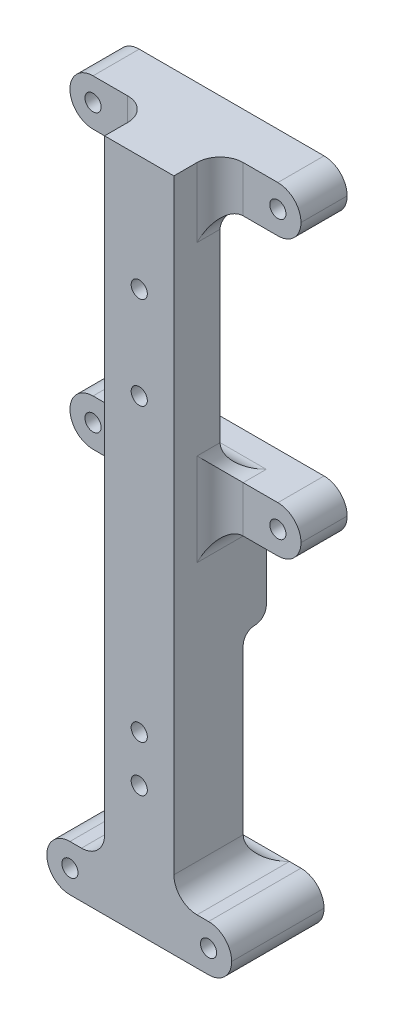
SolidWorks part; units mm, degrees
ref_plane "Front Plane" through (0, 0, 0) normal (0, 0, 1) x (1, 0, 0)
ref_plane "Top Plane" through (0, 0, 0) normal (0, 1, 0) x (1, 0, 0)
ref_plane "Right Plane" through (0, 0, 0) normal (1, 0, 0) x (0, 0, -1)
sketch "Sketch1" plane through (0, 0, 0) normal (0, 0, 1) x (1, 0, 0)
  line L1 (-25, 35) -> (25, 35)
  line L2 (-25, 35) -> (-25, 25)
  line L3 (-25, 25) -> (25, 25)
  line L4 (25, 35) -> (25, 25)
  line L5 (-25, 35) -> (25, 25) construction
  line L6 (-25, 25) -> (25, 35) construction
  line L7 (-25, -25) -> (25, -25)
  line L8 (-25, -25) -> (-25, -35)
  line L9 (-25, -35) -> (25, -35)
  line L10 (25, -25) -> (25, -35)
  line L11 (-25, -25) -> (25, -35) construction
  line L12 (-25, -35) -> (25, -25) construction
  point P0 (0, 30)
  point P5 (0, -30)
  dimension "D1" = 10
  dimension "D2" = 50
  dimension "D3" = 25
  dimension "D4" = 25
extrude "Boss-Extrude1" add sketch "Sketch1" along normal blind 10
sketch "Sketch2" plane through (0, 0, 10) normal (0, 0, 1) x (1, 0, 0)
  line L0 (-25, -35) -> (25, -35) construction
  line L1 (-7.5, 35) -> (7.5, 35)
  line L2 (-7.5, 35) -> (-7.5, -35)
  line L3 (-7.5, -35) -> (7.5, -35)
  line L4 (7.5, 35) -> (7.5, -35)
  line L5 (-7.5, 35) -> (7.5, -35) construction
  line L6 (-7.5, -35) -> (7.5, 35) construction
  point P0 (0, 0)
  dimension "D1" = 15
extrude "Boss-Extrude2" add sketch "Sketch2" along normal blind 10
sketch "Sketch3" plane through (0, 0, 20) normal (0, 0, 1) x (1, 0, 0)
  circle A0 centre (0, 10) radius 1.75
  circle A1 centre (0, -10) radius 1.75
  dimension "D1" = 3.5
  dimension "D2" = 10
  dimension "D3" = 10
extrude "Cut-Extrude1" cut sketch "Sketch3" against normal up to next
sketch "Sketch4" plane through (0, 0, 10) normal (0, 0, 1) x (1, 0, 0)
  line L0 (-25, 35) -> (-25, 25) construction
  line L1 (-7.5, 35) -> (-25, 35) construction
  line L2 (25, 25) -> (25, 35) construction
  line L3 (-7.5, -25) -> (-25, -25) construction
  circle A0 centre (-20, 30) radius 1.75
  circle A1 centre (-20, -30) radius 1.75
  circle A2 centre (20, 30) radius 1.75
  circle A3 centre (20, -30) radius 1.75
  dimension "D1" = 3.5
  dimension "D2" = 5
  dimension "D3" = 5
  dimension "D4" = 5
  dimension "D5" = 5
extrude "Cut-Extrude2" cut sketch "Sketch4" against normal up to next
fillet "Fillet1" [suppressed] radius 5
fillet "Fillet2" radius 5 8 edges at (25, -35, 5) (25, -25, 5) (25, 35, 5) (25, 25, 5) (-25, 35, 5) (-25, 25, 5) (-25, -25, 5) (-25, -35, 5)
fillet "Fillet3" [suppressed] radius 1
fillet "Fillet4" radius 5 2 edges at (0, -25, 10) (0, 25, 10)
fillet "Fillet5" radius 5 2 edges at (7.5, -25, 7.5) (7.5, 25, 7.5)
fillet "Fillet6" radius 5 2 edges at (-7.5, -25, 7.5) (-7.5, 25, 7.5)
sketch "Sketch5" plane through (0, -35, 0) normal (0, -1, 0) x (1, 0, 0)
  line L0 (-20, 0) -> (20, 0) construction
  line L1 (-7.5, 20) -> (7.5, 20)
  line L2 (-7.5, 20) -> (-7.5, 0)
  line L3 (-7.5, 0) -> (7.5, 0)
  line L4 (7.5, 20) -> (7.5, 0)
  line L5 (7.5, 20) -> (7.5, 10) construction
extrude "Boss-Extrude3" add sketch "Sketch5" along normal blind 66
sketch "Sketch6" plane through (0, 0, 0) normal (1, 0, 0) x (0, 0, -1)
  line L0 (0, -101) -> (0, -35) construction
  line L1 (-20, -101) -> (0, -101)
  line L2 (-20, -101) -> (-20, -111)
  line L3 (-20, -111) -> (0, -111)
  line L4 (0, -101) -> (0, -111)
  dimension "D1" = 10
extrude "Boss-Extrude4" add sketch "Sketch6" along normal blind 20 and the other way blind 20
sketch "Sketch7" plane through (0, 0, 20) normal (0, 0, 1) x (1, 0, 0)
  line L0 (-20, -101) -> (-7.5, -101) construction
  circle A0 centre (-15, -106) radius 1.75
  circle A1 centre (15, -106) radius 1.75
  dimension "D2" = 3.5
  dimension "D1" = 5
  dimension "D3" = 30
  dimension "D4" = 15
extrude "Cut-Extrude3" cut sketch "Sketch7" against normal up to next
fillet "Fillet7" radius 5 4 edges at (20, -111, 10) (20, -101, 10) (-20, -111, 10) (-20, -101, 10)
fillet "Fillet9" radius 5 2 edges at (-7.5, -35, 5) (7.5, -35, 5)
fillet "Fillet10" radius 5 4 edges at (7.5, -30, 10) (7.5, 27.5, 10) (-7.5, -30, 10) (-7.5, 27.5, 10)
sketch "Sketch8" plane through (0, 0, 20) normal (0, 0, 1) x (1, 0, 0)
  line L0 (-15, -111) -> (15, -111) construction
  circle A0 centre (0, -73) radius 1.75
  circle A1 centre (0, -83) radius 1.75
  point P4 (0, 0)
  point P7 (0, 0)
  dimension "D1" = 3.5
  dimension "D2" = 28
  dimension "D3" = 10
extrude "Cut-Extrude4" cut sketch "Sketch8" against normal through all
sketch "Sketch11" plane through (0, 0, 0) normal (0, 0, -1) x (-1, 0, 0)
  line L0 (-7.5, -101) -> (-7.5, -40) construction
  line L1 (-7.5, -58) -> (7.5, -58)
  line L2 (-7.5, -58) -> (-7.5, -101)
  line L3 (-7.5, -101) -> (7.5, -101)
  line L4 (7.5, -58) -> (7.5, -101)
  dimension "D1" = 15
extrude "Cut-Extrude5" cut sketch "Sketch11" against normal blind 5
fillet "Fillet11" radius 5 3 edges at (-7.5, -101, 12.5) (7.5, -101, 12.5) (0, -101, 5)
fillet "Fillet13" radius 2.5 2 edges at (0, -58, 0) (0, -58, 5)
